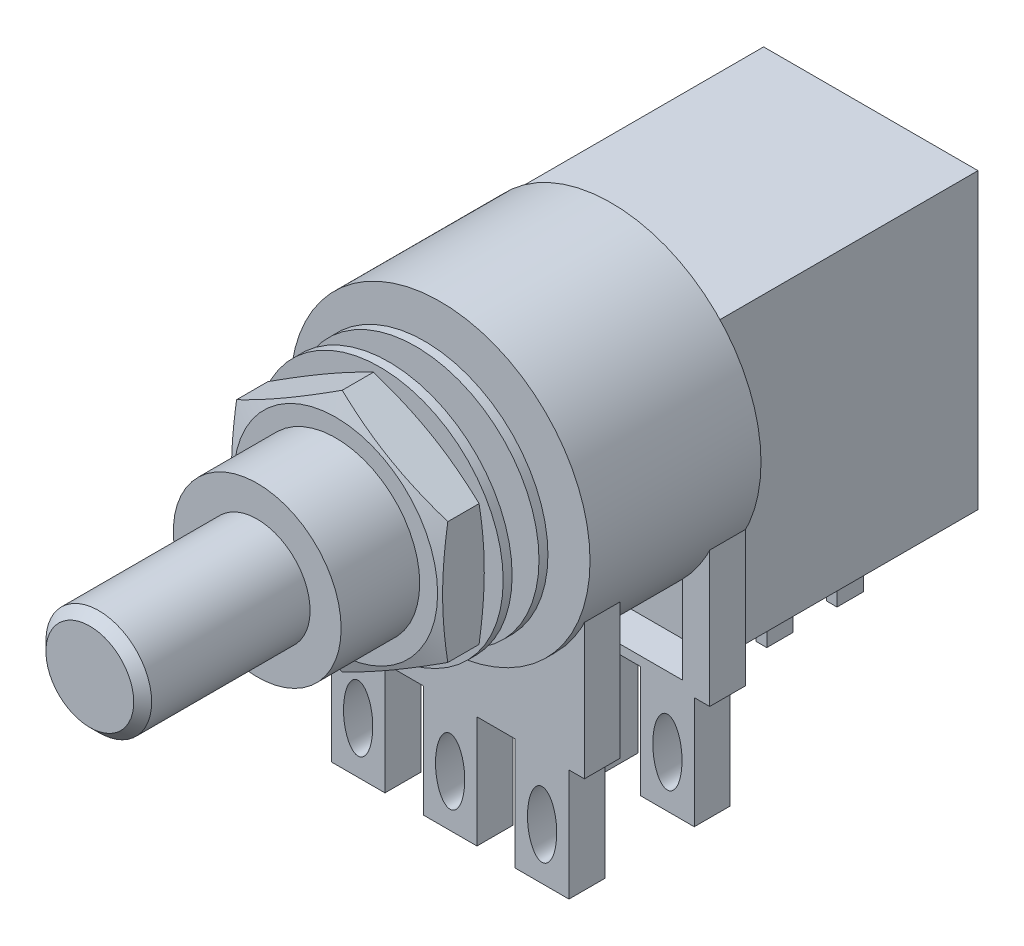
SolidWorks part; units mm, degrees
ref_plane "Front Plane" through (0, 0, 0) normal (0, 0, 1) x (1, 0, 0)
ref_plane "Top Plane" through (0, 0, 0) normal (0, 1, 0) x (1, 0, 0)
ref_plane "Right Plane" through (0, 0, 0) normal (1, 0, 0) x (0, 0, -1)
sketch "Sketch1" plane through (0, 0, 0) normal (0, 0, 1) x (1, 0, 0)
  circle A0 centre (0, 0) radius 5.5118
  circle A1 centre (0, 0) radius 4.7625
  circle A2 centre (0, 0) radius 3
  circle A3 centre (0, 0) radius 8.5
extrude "Boss-Extrude1" add sketch "Sketch1" along normal blind 19 contours A2 region at (0, 0, 0)
extrude "Boss-Extrude2" add sketch "Sketch1<3>" along normal blind 9.5 separate body contours A1 A2 region at (-4.6278, 0, 0)
sketch "Sketch1<3>" plane through (0, 0, 0) normal (0, 0, 1) x (1, 0, 0) same geometry as "Sketch1"
extrude "Boss-Extrude3" add sketch "Sketch1<5>" against normal blind 0.889 contours A0 A1 region at (-5.3559, 0, 0)
sketch "Sketch1<5>" plane through (0, 0, 0) normal (0, 0, 1) x (1, 0, 0) same geometry as "Sketch1"
extrude "Boss-Extrude4" add sketch "Sketch1<6>" against normal blind 9.7028 from offset 0.889 separate body contours A3 A0 region at (-8.2596, 0, 0) offset against normal yes
sketch "Sketch1<6>" plane through (0, 0, 0) normal (0, 0, 1) x (1, 0, 0) same geometry as "Sketch1"
sketch "Sketch2" plane through (0, 0, -10.5918) normal (0, 0, -1) x (-1, 0, 0)
  line L0 (0, 5.7568) -> (0, -10.9056) construction
  line L1 (-6.0833, 5.7568) -> (6.0833, 5.7568)
  line L2 (-6.0833, 5.7568) -> (-6.0833, -10.9056)
  line L3 (-6.0833, -10.9056) -> (6.0833, -10.9056)
  line L4 (6.0833, 5.7568) -> (6.0833, -10.9056)
  line L5 (0, 5.7568) -> (0, 8.5) construction
  dimension "D1" = 12.1666
  dimension "D2" = 16.6624
extrude "Boss-Extrude5" add sketch "Sketch2" along normal blind 14.732 separate body
sketch "Sketch3" plane through (0, 0, -10.5918) normal (0, 0, 1) x (1, 0, 0)
  line L0 (0, -17.78) -> (0, -11.43) construction
  line L1 (-7.62, 0) -> (7.62, 0)
  line L2 (-7.62, 0) -> (-7.62, -11.43)
  line L3 (-7.62, -11.43) -> (7.62, -11.43)
  line L4 (7.62, 0) -> (7.62, -11.43)
  line L5 (-6.7442, -11.43) -> (-3.6962, -11.43)
  line L6 (-6.7442, -11.43) -> (-6.7442, -17.78)
  line L7 (-6.7442, -17.78) -> (-3.6962, -17.78)
  line L8 (-3.6962, -11.43) -> (-3.6962, -17.78)
  line L9 (-1.524, -11.43) -> (1.524, -11.43)
  line L10 (-1.524, -11.43) -> (-1.524, -17.78)
  line L11 (-1.524, -17.78) -> (1.524, -17.78)
  line L12 (1.524, -11.43) -> (1.524, -17.78)
  line L13 (3.6962, -11.43) -> (6.7442, -11.43)
  line L14 (3.6962, -11.43) -> (3.6962, -17.78)
  line L15 (3.6962, -17.78) -> (6.7442, -17.78)
  line L16 (6.7442, -11.43) -> (6.7442, -17.78)
  line L17 (-3.6962, -17.78) -> (-1.524, -17.78) construction
  line L18 (1.524, -17.78) -> (3.6962, -17.78) construction
  ellipse E0 centre (-5.2202, -14.8704) end of major axis (-5.2202, -13.0062) minor radius 0.8296
  ellipse E1 centre (0, -14.8704) end of major axis (0, -16.7346) minor radius 0.8296
  ellipse E2 centre (5.2202, -14.8704) end of major axis (5.2202, -13.0062) minor radius 0.8296
  point P17 (0, -11.43)
  line M1 (6.0833, -10.9056) -> (6.0833, 5.7568)
  line M3 (-6.0833, 5.7568) -> (-6.0833, -10.9056)
  line M4 (-6.0833, -10.9056) -> (6.0833, -10.9056)
  dimension "D1" = 15.24
  dimension "D2" = 11.43
extrude "Boss-Extrude6" add sketch "Sketch3" along normal blind 2.032 separate body contours L4 L1 L2 L3 M1 M4 M3 | L16 L3 L14 L15 E2 | L12 L3 L10 L11 E1 | L8 L3 L6 L7 E0 region at (-6.8517, -0.1905, -10.5918) region at (-5.2202, -11.5004, -10.5918) region at (0, -11.5004, -10.5918) region at (6.6737, -14.605, -10.5918)
extrude "Boss-Extrude9" add sketch "Sketch3<3>" against normal blind 2.032 from offset 9.144 separate body contours L8 L3 L6 L7 E0 | L12 L3 L10 L11 E1 | L16 L3 L14 L15 E2 | L4 L1 L2 L3 M1 M4 M3 | L1 M3 M4 M1 region at (-6.8517, -0.1905, -10.5918) region at (0, -5.4528, -10.5918) region at (-5.2202, -11.5004, -10.5918) region at (0, -11.5004, -10.5918) region at (6.6737, -14.605, -10.5918)
sketch "Sketch3<3>" plane through (0, 0, -10.5918) normal (0, 0, 1) x (1, 0, 0) same geometry as "Sketch3"
sketch "Sketch4" plane through (0, -10.9056, 0) normal (0, -1, 0) x (1, 0, 0)
  line L0 (-2.1971, -14.1224) -> (-2.1971, -18.1102) construction
  line L1 (-2.8067, -12.6238) -> (-2.1971, -12.6238)
  line L2 (-2.8067, -12.6238) -> (-2.8067, -14.1224)
  line L3 (-2.8067, -14.1224) -> (-2.1971, -14.1224)
  line L4 (-2.1971, -12.6238) -> (-2.1971, -14.1224)
  line L5 (-2.1971, -18.1102) -> (-2.1971, -22.098) construction
  line L6 (-2.8067, -16.6116) -> (-2.1971, -16.6116)
  line L7 (-2.8067, -16.6116) -> (-2.8067, -18.1102)
  line L8 (-2.8067, -18.1102) -> (-2.1971, -18.1102)
  line L9 (-2.1971, -16.6116) -> (-2.1971, -18.1102)
  line L10 (-2.1971, -12.6238) -> (2.1971, -12.6238) construction
  line L11 (-2.8067, -20.5994) -> (-2.1971, -20.5994)
  line L12 (-2.8067, -20.5994) -> (-2.8067, -22.098)
  line L13 (-2.8067, -22.098) -> (-2.1971, -22.098)
  line L14 (-2.1971, -20.5994) -> (-2.1971, -22.098)
  line L15 (-2.1971, -14.1224) -> (2.8067, -14.1224) construction
  line L16 (2.8067, -14.1224) -> (2.8067, -18.1102) construction
  line L17 (2.1971, -12.6238) -> (2.8067, -12.6238)
  line L18 (2.1971, -12.6238) -> (2.1971, -14.1224)
  line L19 (2.1971, -14.1224) -> (2.8067, -14.1224)
  line L20 (2.8067, -12.6238) -> (2.8067, -14.1224)
  line L21 (2.8067, -18.1102) -> (2.8067, -22.098) construction
  line L22 (2.1971, -16.6116) -> (2.8067, -16.6116)
  line L23 (2.1971, -16.6116) -> (2.1971, -18.1102)
  line L24 (2.1971, -18.1102) -> (2.8067, -18.1102)
  line L25 (2.8067, -16.6116) -> (2.8067, -18.1102)
  line L26 (2.1971, -12.6238) -> (2.2543, -12.64) construction
  line L27 (2.1971, -20.5994) -> (2.8067, -20.5994)
  line L28 (2.1971, -20.5994) -> (2.1971, -22.098)
  line L29 (2.1971, -22.098) -> (2.8067, -22.098)
  line L30 (2.8067, -20.5994) -> (2.8067, -22.098)
  line L31 (0, -25.3238) -> (0, -10.5918) construction
  line L32 (6.0833, -25.3238) -> (-6.0833, -25.3238) construction
  line L33 (-1.524, -10.5918) -> (1.524, -10.5918) construction
  line L34 (0, -10.5918) -> (0, -12.6238) construction
extrude "Boss-Extrude10" add sketch "Sketch4" along normal blind 4.064 separate body
chamfer "Chamfer1" distance 0.508 angle 45 1 edges at (3, 0, 19)
fillet "Fillet1" [suppressed] radius 0.508
ref_plane "Plane1" through (0, 0, 2.032) normal (0, 0, 1) x (1, 0, 0)
sketch "Sketch6" plane through (0, 0, 2.032) normal (0, 0, 1) x (1, 0, 0)
  circle A0 centre (0, 0) radius 7
  circle A1 centre (0, 0) radius 4.75
extrude "Boss-Extrude11" add sketch "Sketch6" along normal blind 0.508 separate body
sketch "Sketch8" plane through (0, 0, 2.54) normal (0, 0, 1) x (1, 0, 0)
  line L0 (0, 6.9217) -> (-5.9944, 3.4609)
  line L1 (-5.9944, 3.4609) -> (-5.9944, -3.4609)
  line L2 (-5.9944, -3.4609) -> (0, -6.9217)
  line L3 (0, -6.9217) -> (5.9944, -3.4609)
  line L4 (5.9944, -3.4609) -> (5.9944, 3.4609)
  line L5 (5.9944, 3.4609) -> (0, 6.9217)
  circle A0 centre (0, 0) radius 6.9217 construction
  circle A1 centre (0, 0) radius 4.7625
  dimension "D1" = 11.9888
extrude "Boss-Extrude12" add sketch "Sketch8" along normal blind 2.5
sketch "Sketch9" plane through (0, 0, 0) normal (0, 1, 0) x (1, 0, 0)
  line L0 (5.7789, -5.04) -> (8.5439, -4.1625)
  line L2 (8.5439, -4.1625) -> (8.5439, -5.04)
  line L3 (8.5439, -5.04) -> (5.7789, -5.04)
  line L4 (0, 0) -> (0, -5.04) construction
  line L5 (0, -5.04) -> (5.9944, -5.04) construction
  line L6 (5.9944, -3.79) -> (9.5209, -3.79) construction
  line L7 (5.9944, -5.04) -> (5.9944, -2.54) construction
  line L8 (8.5439, -2.54) -> (5.7789, -2.54)
  line L9 (8.5439, -3.4175) -> (8.5439, -2.54)
  line L10 (5.7789, -2.54) -> (8.5439, -3.4175)
revolve "Cut-Revolve3" cut sketch "Sketch9" angle 360 about L4
extrude "Boss-Extrude15" add sketch "Sketch6<2>" along normal blind 0.508 from surface separate body contours A0 A1 region at (-6.802, 0, 2.032) starting at plane "Front Plane"
sketch "Sketch6<2>" plane through (0, 0, 2.032) normal (0, 0, 1) x (1, 0, 0) same geometry as "Sketch6"
